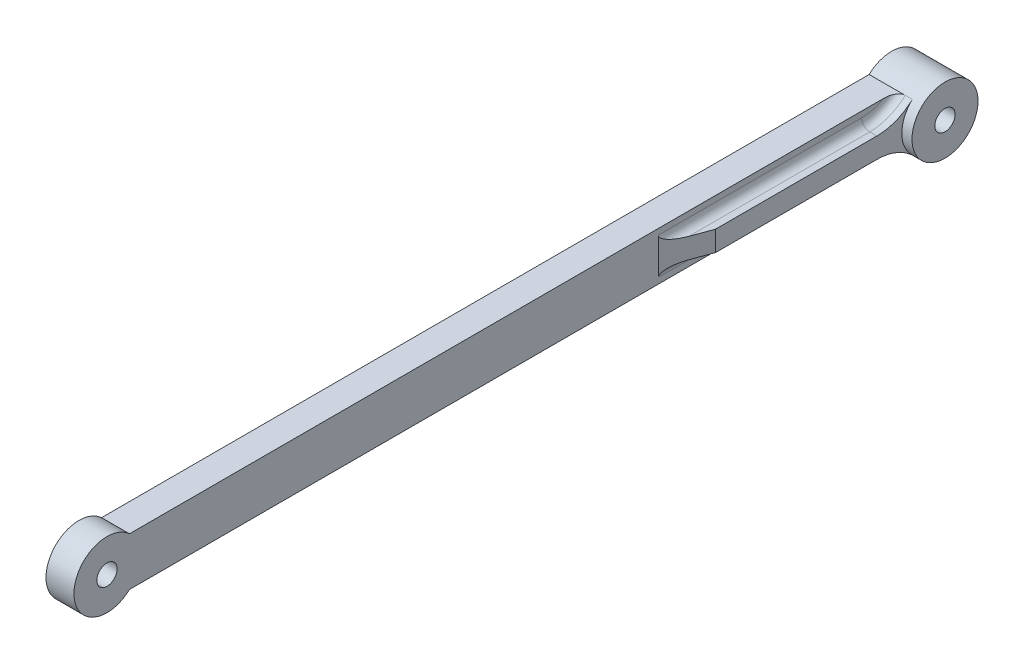
SolidWorks part; units mm, degrees
ref_plane "Plan de face" through (0, 0, 0) normal (0, 0, 1) x (1, 0, 0)
ref_plane "Plan de dessus" through (0, 0, 0) normal (0, 1, 0) x (1, 0, 0)
ref_plane "Plan de droite" through (0, 0, 0) normal (1, 0, 0) x (0, 0, -1)
sketch "Sketch1" plane through (0, 0, 0) normal (1, 0, 0) x (0, 0, -1)
  line L0 (0, 0) -> (160, 0) construction
  line L1 (4.4371, 4.75) -> (155.5629, 4.75)
  line L2 (4.4371, -4.75) -> (155.5629, -4.75)
  arc A0 (4.4371, 4.75) -> (4.4371, -4.75) centre (0, 0) ccw
  circle A1 centre (0, 0) radius 2
  arc A2 (155.5629, -4.75) -> (155.5629, 4.75) centre (160, 0) ccw
  circle A3 centre (160, 0) radius 2
  dimension "D2" = 13
  dimension "D3" = 4
  dimension "D1" = 160
  dimension "D4" = 4.75
extrude "Boss-Extrude1" add sketch "Sketch1" along normal blind 5.5
sketch "Sketch2" plane through (5.5, 0, 0) normal (1, 0, 0) x (0, 0, -1)
  circle A1 centre (160, 0) radius 6.5
  circle A2 centre (160, 0) radius 2 construction
  circle A3 centre (160, 0) radius 2
extrude "Boss-Extrude3" add sketch "Sketch2" along normal blind 5
sketch "Sketch3" plane through (5.5, 0, 0) normal (1, 0, 0) x (0, 0, -1)
  line L0 (160, 0) -> (130.0374, 0) construction
  line L1 (148.5904, -2) -> (108.5904, -2)
  line L2 (108.5904, 2) -> (108.5904, -2)
  line L3 (148.5904, 2) -> (108.5904, 2)
  arc A0 (155.5629, 4.75) -> (155.5629, -4.75) centre (160, 0) ccw construction
  arc A1 (155.5629, 4.75) -> (155.5629, -4.75) centre (160, 0) ccw
  arc A2 (155.5629, 4.75) -> (148.5904, 2) centre (148.5904, 12.2143) cw
  arc A3 (155.5629, -4.75) -> (148.5904, -2) centre (148.5904, -12.2143) ccw
  circle A4 centre (160, 0) radius 6.5 construction
  circle A5 centre (160, 0) radius 6.5 construction
  dimension "D1" = 4
  dimension "D2" = 40
extrude "Boss-Extrude4" add sketch "Sketch3" along normal blind 3
chamfer "Chamfer1" distance 3 angle 70 1 edges at (8.5, 0, -108.5904) first distance on face at (7, 0, -108.5904)
fillet "Fillet1" radius 1.6 4 edges at (5.5, 2.7123, -152.338) (5.5, -2.7123, -152.338) (5.5, 2, -128.5904) (5.5, -2, -128.5904)
equation "\"D4@Sketch1\"=9.5/2"
equation "\"Longueur1\"= 160mm"
equation "\"Longueur2\"= 180mm"
equation "\"D1@Sketch1\"=\"Longueur1\""
